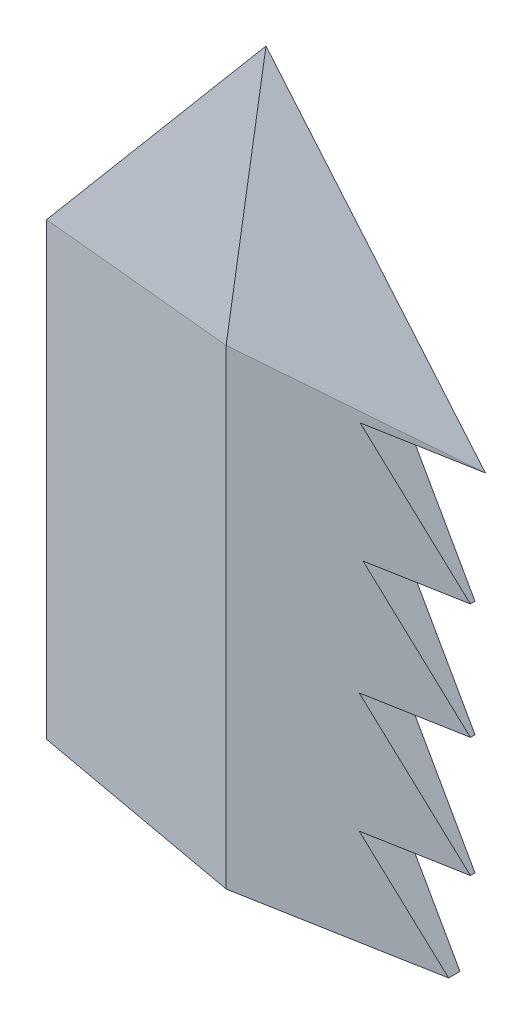
SolidWorks part; units mm, degrees
ref_plane "Front Plane" through (0, 0, 0) normal (0, 0, 1) x (1, 0, 0)
ref_plane "Top Plane" through (0, 0, 0) normal (0, 1, 0) x (1, 0, 0)
ref_plane "Right Plane" through (0, 0, 0) normal (1, 0, 0) x (0, 0, -1)
sketch "Sketch1" plane through (0, 0, 0) normal (0, 0, 1) x (1, 0, 0)
  line L0 (101.7924, 735.6565) -> (49.4049, 673.5573)
  line L1 (49.4049, 673.5573) -> (49.4049, 396.4974)
  line L2 (49.4049, 396.4974) -> (154.1799, 396.4974)
  line L3 (154.1799, 396.4974) -> (154.1799, 556.6364)
  line L4 (154.1799, 673.5573) -> (101.7924, 735.6565)
  line L5 (154.1799, 673.5573) -> (128.876, 673.5573)
  line L6 (128.876, 673.5573) -> (151.1488, 645.2298)
  line L7 (151.1488, 645.2298) -> (129.452, 645.2298)
  line L8 (129.452, 645.2298) -> (151.1488, 617.6349)
  line L9 (151.1488, 617.6349) -> (128.684, 617.6349)
  line L10 (128.684, 617.6349) -> (151.1488, 589.0632)
  line L11 (151.1488, 589.0632) -> (128.684, 589.0632)
  line L12 (128.684, 589.0632) -> (154.1799, 556.6364)
  point P2 (101.7924, 396.4974)
  dimension "D1" = 104.775
extrude "Boss-Extrude1" add sketch "Sketch1" along normal blind 9.525 and the other way blind 9.525
sketch "Sketch2" plane through (0, 396.4974, 0) normal (0, -1, 0) x (-1, 0, 0)
  line L0 (-49.4049, 0) -> (-101.7924, -9.525)
  line L1 (-49.4049, 9.525) -> (-49.4049, -9.525) construction
  line L2 (-49.4049, -9.525) -> (-154.1799, -9.525) construction
  line L3 (-101.7924, -9.525) -> (-154.1799, 0)
  line L4 (-154.1799, 9.525) -> (-154.1799, -9.525) construction
  line L5 (-154.1799, 0) -> (-159.6573, 0)
  line L6 (-159.6573, 0) -> (-159.6573, -13.6491)
  line L7 (-159.6573, -13.6491) -> (-44.1585, -13.6491)
  line L8 (-44.1585, -13.6491) -> (-44.1585, 0)
  line L9 (-44.1585, 0) -> (-49.4049, 0)
extrude "Cut-Extrude1" cut sketch "Sketch2" against normal through all
sketch "Sketch3" plane through (0, 396.4974, 0) normal (0, -1, 0) x (1, 0, 0)
  line L0 (49.4049, 0) -> (101.7924, -9.525)
  line L1 (101.7924, -9.525) -> (154.1799, 0)
  line L2 (154.1799, 0) -> (159.5806, 0)
  line L3 (159.5806, 0) -> (159.5806, -14.5007)
  line L4 (159.5806, -14.5007) -> (43.682, -14.5007)
  line L5 (43.682, -14.5007) -> (43.682, 0)
  line L6 (43.682, 0) -> (49.4049, 0)
extrude "Cut-Extrude2" cut sketch "Sketch3" against normal through all
sketch "Sketch4" plane through (4.9338, 0, 27.1357) normal (0.1789, 0, 0.9839) x (0.9839, 0, -0.1789)
  line L0 (98.4466, 735.6565) -> (98.4466, 396.4974) construction
  point P0 (98.4466, 678.5065)
  dimension "D1" = 57.15
ref_plane "Plane1" through (26.4305, 22.297, 133.782) normal (0.1913, 0.1614, 0.9682) x (0.9815, -0.0314, -0.1887)
sketch "Sketch5" plane through (26.4305, 22.297, 133.782) normal (0.1913, 0.1614, 0.9682) x (0.9815, -0.0314, -0.1887)
  line L1 (40.4892, 768.9526) -> (138.0076, 768.9526)
  line L2 (40.4892, 768.9526) -> (40.4892, 632.533)
  line L3 (40.4892, 632.533) -> (138.0076, 632.533)
  line L4 (138.0076, 768.9526) -> (138.0076, 632.533)
extrude "Cut-Extrude3" cut sketch "Sketch5" along normal through all
ref_plane "Plane2" through (-18.9819, 16.0133, 96.0799) normal (-0.1913, 0.1614, 0.9682) x (0.9815, 0.0314, 0.1887)
sketch "Sketch6" plane through (-18.9819, 16.0133, 96.0799) normal (-0.1913, 0.1614, 0.9682) x (0.9815, 0.0314, 0.1887)
  line L1 (61.3232, 620.6538) -> (136.4239, 620.6538)
  line L2 (61.3232, 620.6538) -> (61.3232, 774.9318)
  line L3 (61.3232, 774.9318) -> (136.4239, 774.9318)
  line L4 (136.4239, 620.6538) -> (136.4239, 774.9318)
extrude "Cut-Extrude4" cut sketch "Sketch6" along normal through all
mirror "Mirror1" about plane through (0, 0, 0) normal (0, 0, 1) of "Cut-Extrude4", "Cut-Extrude3"
sketch "Sketch7" plane through (0, 396.4974, 0) normal (0, -1, 0) x (1, 0, 0)
  circle A0 centre (101.7924, 0) radius 4.7625
  dimension "D1" = 9.525
extrude "Cut-Extrude5" cut sketch "Sketch7" against normal blind 254
sketch "Sketch8" plane through (0, 0, 0) normal (0, 0, 1) x (1, 0, 0)
  line L0 (-21.6446, 566.0769) -> (201.353, 566.0769)
  line L1 (101.7924, 735.6565) -> (101.7924, 396.4974)
  line L2 (49.4049, 396.4974) -> (101.7924, 396.4974) construction
  line L3 (-21.6446, 566.0769) -> (-21.6446, 347.6285)
  line L4 (-21.6446, 347.6285) -> (201.353, 347.6285)
  line L5 (201.353, 347.6285) -> (201.353, 566.0769)
  point P7 (101.7924, 566.0769)
extrude "Cut-Extrude6" cut sketch "Sketch8" against normal through all and the other way through all contours L5 L4 L3 L0 | L4 L5 L0 L3 region at (89.8542, 456.8527, 0)
sketch "Sketch11" plane through (0, 566.0769, 0) normal (0, -1, 0) x (1, 0, 0)
  circle A0 centre (89.0924, 0) radius 1.5875
  circle A1 centre (114.4924, 0) radius 1.5875
  circle A2 centre (101.7924, 0) radius 4.7625 construction
  dimension "D1" = 12.7
  dimension "D2" = 12.7
  dimension "D3" = 3.175
extrude "Cut-Extrude9" cut sketch "Sketch11" against normal blind 12.7
